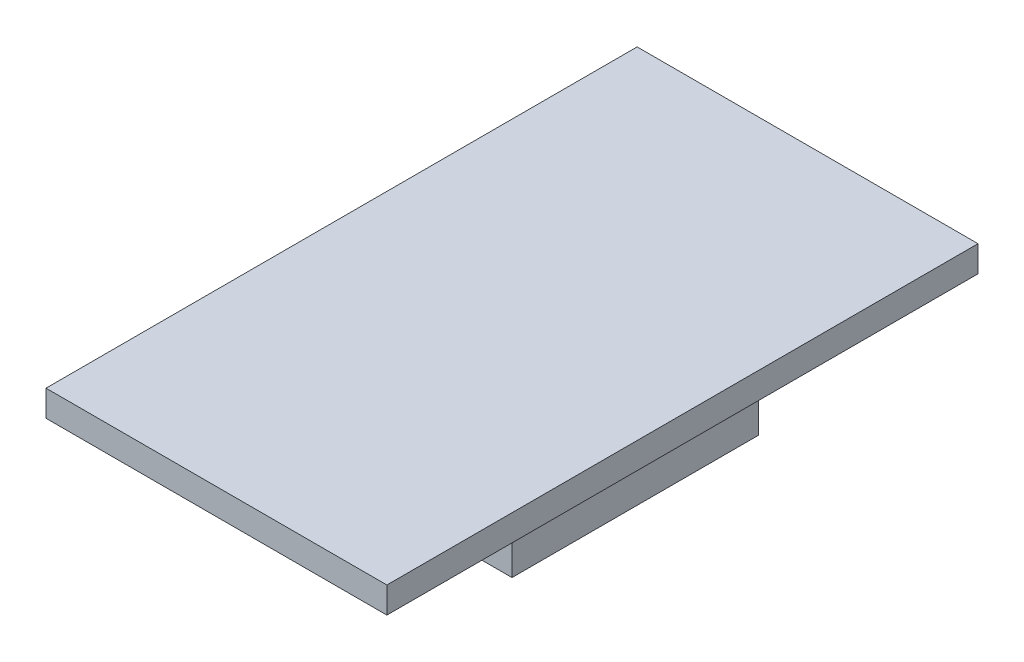
SolidWorks part; units mm, degrees
ref_plane "Спереди" through (0, 0, 0) normal (0, 0, 1) x (1, 0, 0)
ref_plane "Сверху" through (0, 0, 0) normal (0, 1, 0) x (1, 0, 0)
ref_plane "Справа" through (0, 0, 0) normal (1, 0, 0) x (0, 0, -1)
sketch "Sketch1" plane through (0, 0, 0) normal (0, 1, 0) x (1, 0, 0)
  line L1 (3.46, -6) -> (-3.46, -6)
  line L2 (3.46, -6) -> (3.46, 6)
  line L3 (3.46, 6) -> (-3.46, 6)
  line L4 (-3.46, -6) -> (-3.46, 6)
  line L5 (3.46, -6) -> (-3.46, 6) construction
  line L6 (3.46, 6) -> (-3.46, -6) construction
  point P0 (0, 0)
  dimension "D1" = 12
  dimension "D2" = 6.92
extrude "Boss-Extrude1" add sketch "Sketch1" along normal blind 0.53
sketch "Sketch2" plane through (0, 0, 0) normal (0, -1, 0) x (1, 0, 0)
  line L1 (2.5, 2.5) -> (-2.5, 2.5)
  line L2 (2.5, 2.5) -> (2.5, -2.5)
  line L3 (2.5, -2.5) -> (-2.5, -2.5)
  line L4 (-2.5, 2.5) -> (-2.5, -2.5)
  line L5 (2.5, 2.5) -> (-2.5, -2.5) construction
  line L6 (2.5, -2.5) -> (-2.5, 2.5) construction
  point P0 (0, 0)
  dimension "D1" = 5
  dimension "D2" = 5
extrude "Boss-Extrude2" add sketch "Sketch2" along normal blind 1.57
sketch "Sketch3" plane through (0, -1.57, 0) normal (0, -1, 0) x (1, 0, 0)
  circle A0 centre (0, 0) radius 2
extrude "Cut-Extrude1" cut sketch "Sketch3" against normal blind 0.2
chamfer "Chamfer1" distance 0.1 angle 45 1 edges at (0, -1.57, -2)
sketch "Sketch4" plane through (0, 0, 0) normal (0, -1, 0) x (1, 0, 0)
  line L8 (3.46, -6) -> (-3.46, -6) construction
  line L13 (-2.351, -3.4515) -> (-3.46, -3.4515)
  line L14 (-3.46, -3.4515) -> (-3.46, -5.1515)
  line L15 (-3.46, -5.1515) -> (-2.351, -5.1515)
  line L16 (-9.0262, 0) -> (8.7663, 0) construction
  line L17 (-3.46, 3.4515) -> (-3.46, 5.1515)
  line L18 (-2.351, 3.4515) -> (-3.46, 3.4515)
  line L19 (-3.46, 5.1515) -> (-2.351, 5.1515)
  line L20 (-3.46, -6) -> (-3.46, 6) construction
  line L21 (-3.46, 0.85) -> (-3.46, -0.85)
  arc A2 (-2.351, -3.4515) -> (-2.351, -5.1515) centre (-2.351, -4.3015) cw
  arc A4 (-2.351, 3.4515) -> (-2.351, 5.1515) centre (-2.351, 4.3015) ccw
  arc A5 (-3.46, 0.85) -> (-3.46, -0.85) centre (-3.46, 0) cw
  point P14 (-2.5468, -6)
  dimension "D5" = 0.85
  dimension "D6" = 0.85
  dimension "D4" = 1.7
sketch "Sketch6" plane through (0, 0, 0) normal (0, -1, 0) x (1, 0, 0)
  line L1 (-1, -4.85) -> (1, -4.85)
  line L2 (-1, -4.85) -> (-1, -3.65)
  line L3 (-1, -3.65) -> (1, -3.65)
  line L4 (1, -4.85) -> (1, -3.65)
  point P7 (0, 0)
extrude "Boss-Extrude3" add sketch "Sketch6" along normal blind 0.45
extrude "Cut-Extrude2" cut sketch "Sketch4" against normal blind 0.1
